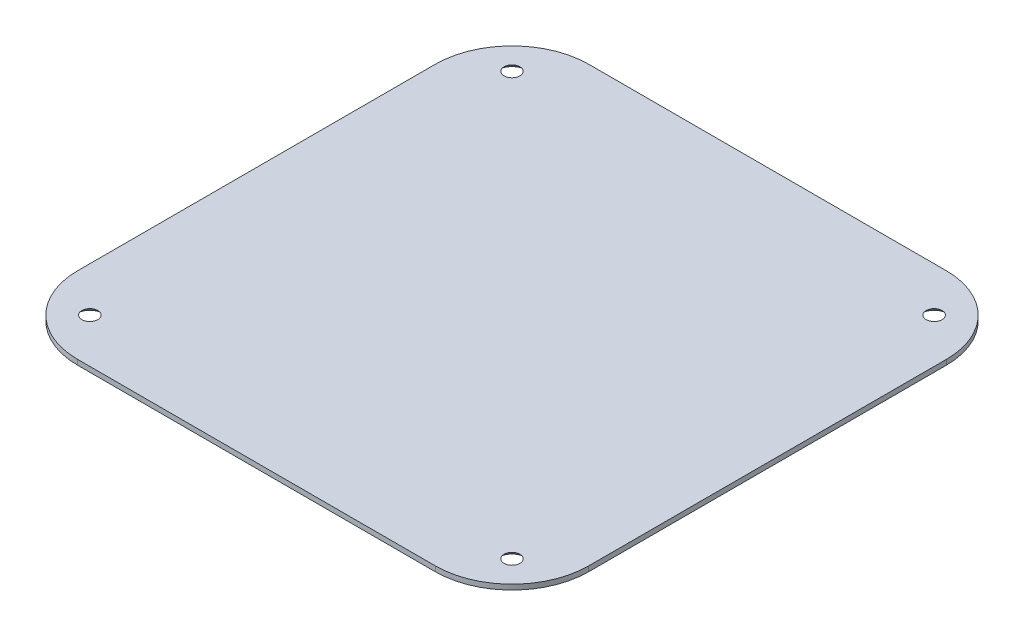
SolidWorks part; units mm, degrees
ref_plane "Front Plane" through (0, 0, 0) normal (0, 0, 1) x (1, 0, 0)
ref_plane "Top Plane" through (0, 0, 0) normal (0, 1, 0) x (1, 0, 0)
ref_plane "Right Plane" through (0, 0, 0) normal (1, 0, 0) x (0, 0, -1)
sketch "Sketch1" plane through (0, 0, 0) normal (0, 1, 0) x (1, 0, 0)
  line L0 (-80, 100) -> (-80, -100) construction
  line L15 (70, -100) -> (-70, -100)
  line L16 (100, -70) -> (100, 70)
  line L17 (70, 100) -> (-70, 100)
  line L18 (-100, -70) -> (-100, 70)
  line L35 (100, -100) -> (-100, 100) construction
  line L45 (100, 100) -> (-100, -100) construction
  line L46 (80, 100) -> (80, -100) construction
  line L53 (-100, 80) -> (100, 80) construction
  line L54 (-100, -80) -> (100, -80) construction
  line L82 (-100, 0) -> (100, 0) construction
  line L83 (-100, 40) -> (100, 40) construction
  line L120 (-100, -40) -> (100, -40) construction
  line L121 (0, 100) -> (0, -100) construction
  line L122 (-40, 100) -> (-40, -100) construction
  line L123 (40, 100) -> (40, -100) construction
  line L124 (-42.5, 70) -> (-42.5, 50)
  line L125 (-50, 2.5) -> (-70, 2.5)
  line L126 (-42.5, 10) -> (-42.5, 30)
  line L127 (-50, 37.5) -> (-70, 37.5)
  line L128 (-77.5, 10) -> (-77.5, 30)
  line L129 (-42.5, 2.5) -> (-77.5, 37.5) construction
  line L130 (-42.5, 37.5) -> (-77.5, 2.5) construction
  line L131 (-50, 42.5) -> (-70, 42.5)
  line L132 (-77.5, 70) -> (-77.5, 50)
  line L133 (-50, 77.5) -> (-70, 77.5)
  line L134 (-30, 77.5) -> (-10, 77.5)
  line L135 (-2.5, 70) -> (-2.5, 50)
  line L136 (-37.5, 70) -> (-37.5, 50)
  line L137 (-30, 42.5) -> (-10, 42.5)
  line L138 (-30, 37.5) -> (-10, 37.5)
  line L139 (-37.5, 10) -> (-37.5, 30)
  line L140 (-30, 2.5) -> (-10, 2.5)
  line L141 (-2.5, 10) -> (-2.5, 30)
  line L142 (42.5, 10) -> (42.5, 30)
  line L143 (50, 2.5) -> (70, 2.5)
  line L144 (77.5, 10) -> (77.5, 30)
  line L145 (50, 37.5) -> (70, 37.5)
  line L146 (42.5, 70) -> (42.5, 50)
  line L147 (50, 77.5) -> (70, 77.5)
  line L148 (77.5, 70) -> (77.5, 50)
  line L149 (50, 42.5) -> (70, 42.5)
  line L150 (2.5, 70) -> (2.5, 50)
  line L151 (30, 77.5) -> (10, 77.5)
  line L152 (37.5, 70) -> (37.5, 50)
  line L153 (30, 42.5) -> (10, 42.5)
  line L154 (37.5, 10) -> (37.5, 30)
  line L155 (30, 37.5) -> (10, 37.5)
  line L156 (2.5, 10) -> (2.5, 30)
  line L157 (30, 2.5) -> (10, 2.5)
  line L158 (-42.5, -70) -> (-42.5, -50)
  line L159 (-50, -77.5) -> (-70, -77.5)
  line L160 (-77.5, -70) -> (-77.5, -50)
  line L161 (-50, -42.5) -> (-70, -42.5)
  line L162 (-2.5, -70) -> (-2.5, -50)
  line L163 (-30, -77.5) -> (-10, -77.5)
  line L164 (-37.5, -70) -> (-37.5, -50)
  line L165 (-30, -42.5) -> (-10, -42.5)
  line L166 (37.5, -70) -> (37.5, -50)
  line L167 (30, -77.5) -> (10, -77.5)
  line L168 (2.5, -70) -> (2.5, -50)
  line L169 (30, -42.5) -> (10, -42.5)
  line L170 (77.5, -70) -> (77.5, -50)
  line L171 (50, -77.5) -> (70, -77.5)
  line L172 (42.5, -70) -> (42.5, -50)
  line L173 (50, -42.5) -> (70, -42.5)
  line L174 (50, -37.5) -> (70, -37.5)
  line L175 (77.5, -10) -> (77.5, -30)
  line L176 (50, -2.5) -> (70, -2.5)
  line L177 (42.5, -10) -> (42.5, -30)
  line L178 (37.5, -10) -> (37.5, -30)
  line L179 (30, -2.5) -> (10, -2.5)
  line L180 (2.5, -10) -> (2.5, -30)
  line L181 (30, -37.5) -> (10, -37.5)
  line L182 (-30, -37.5) -> (-10, -37.5)
  line L183 (-37.5, -10) -> (-37.5, -30)
  line L184 (-2.5, -10) -> (-2.5, -30)
  line L185 (-30, -2.5) -> (-10, -2.5)
  line L186 (-42.5, -10) -> (-42.5, -30)
  line L187 (-50, -37.5) -> (-70, -37.5)
  line L188 (-77.5, -10) -> (-77.5, -30)
  line L189 (-50, -2.5) -> (-70, -2.5)
  arc A0 (100, 70) -> (70, 100) centre (70, 70) ccw
  arc A1 (70, -100) -> (100, -70) centre (70, -70) ccw
  arc A2 (-70, -100) -> (-100, -70) centre (-70, -70) cw
  arc A3 (-70, 100) -> (-100, 70) centre (-70, 70) ccw
  circle A5 centre (-82.6, 82.6) radius 2.6
  circle A6 centre (82.6, 82.6) radius 2.6
  circle A7 centre (82.6, -82.6) radius 2.6
  circle A8 centre (-82.6, -82.6) radius 2.6
  arc A9 (-70, 2.5) -> (-77.5, 10) centre (-70, 10) cw
  arc A10 (-50, 2.5) -> (-42.5, 10) centre (-50, 10) ccw
  arc A11 (-42.5, 30) -> (-50, 37.5) centre (-50, 30) ccw
  arc A12 (-70, 37.5) -> (-77.5, 30) centre (-70, 30) ccw
  arc A13 (-50, 77.5) -> (-42.5, 70) centre (-50, 70) cw
  arc A14 (-42.5, 50) -> (-50, 42.5) centre (-50, 50) cw
  arc A15 (-70, 42.5) -> (-77.5, 50) centre (-70, 50) cw
  arc A16 (-70, 77.5) -> (-77.5, 70) centre (-70, 70) ccw
  arc A17 (-30, 77.5) -> (-37.5, 70) centre (-30, 70) ccw
  arc A18 (-10, 77.5) -> (-2.5, 70) centre (-10, 70) cw
  arc A19 (-37.5, 50) -> (-30, 42.5) centre (-30, 50) ccw
  arc A20 (-10, 42.5) -> (-2.5, 50) centre (-10, 50) ccw
  arc A21 (-10, 37.5) -> (-2.5, 30) centre (-10, 30) cw
  arc A22 (-37.5, 30) -> (-30, 37.5) centre (-30, 30) cw
  arc A23 (-30, 2.5) -> (-37.5, 10) centre (-30, 10) cw
  arc A24 (-10, 2.5) -> (-2.5, 10) centre (-10, 10) ccw
  arc A25 (42.5, 30) -> (50, 37.5) centre (50, 30) cw
  arc A26 (50, 2.5) -> (42.5, 10) centre (50, 10) cw
  arc A27 (70, 2.5) -> (77.5, 10) centre (70, 10) ccw
  arc A28 (70, 37.5) -> (77.5, 30) centre (70, 30) cw
  arc A29 (50, 77.5) -> (42.5, 70) centre (50, 70) ccw
  arc A30 (70, 77.5) -> (77.5, 70) centre (70, 70) cw
  arc A31 (70, 42.5) -> (77.5, 50) centre (70, 50) ccw
  arc A32 (42.5, 50) -> (50, 42.5) centre (50, 50) ccw
  arc A33 (10, 42.5) -> (2.5, 50) centre (10, 50) cw
  arc A34 (10, 77.5) -> (2.5, 70) centre (10, 70) ccw
  arc A35 (30, 77.5) -> (37.5, 70) centre (30, 70) cw
  arc A36 (37.5, 50) -> (30, 42.5) centre (30, 50) cw
  arc A37 (37.5, 30) -> (30, 37.5) centre (30, 30) ccw
  arc A38 (10, 37.5) -> (2.5, 30) centre (10, 30) ccw
  arc A39 (10, 2.5) -> (2.5, 10) centre (10, 10) cw
  arc A40 (30, 2.5) -> (37.5, 10) centre (30, 10) ccw
  arc A41 (-42.5, -50) -> (-50, -42.5) centre (-50, -50) ccw
  arc A42 (-50, -77.5) -> (-42.5, -70) centre (-50, -70) ccw
  arc A43 (-70, -77.5) -> (-77.5, -70) centre (-70, -70) cw
  arc A44 (-70, -42.5) -> (-77.5, -50) centre (-70, -50) ccw
  arc A45 (-10, -77.5) -> (-2.5, -70) centre (-10, -70) ccw
  arc A46 (-30, -77.5) -> (-37.5, -70) centre (-30, -70) cw
  arc A47 (-37.5, -50) -> (-30, -42.5) centre (-30, -50) cw
  arc A48 (-10, -42.5) -> (-2.5, -50) centre (-10, -50) cw
  arc A49 (37.5, -50) -> (30, -42.5) centre (30, -50) ccw
  arc A50 (30, -77.5) -> (37.5, -70) centre (30, -70) ccw
  arc A51 (10, -77.5) -> (2.5, -70) centre (10, -70) cw
  arc A52 (10, -42.5) -> (2.5, -50) centre (10, -50) ccw
  arc A53 (70, -42.5) -> (77.5, -50) centre (70, -50) cw
  arc A54 (70, -77.5) -> (77.5, -70) centre (70, -70) ccw
  arc A55 (50, -77.5) -> (42.5, -70) centre (50, -70) cw
  arc A56 (42.5, -50) -> (50, -42.5) centre (50, -50) cw
  arc A57 (70, -37.5) -> (77.5, -30) centre (70, -30) ccw
  arc A58 (70, -2.5) -> (77.5, -10) centre (70, -10) cw
  arc A59 (50, -2.5) -> (42.5, -10) centre (50, -10) ccw
  arc A60 (42.5, -30) -> (50, -37.5) centre (50, -30) ccw
  arc A61 (37.5, -30) -> (30, -37.5) centre (30, -30) cw
  arc A62 (30, -2.5) -> (37.5, -10) centre (30, -10) cw
  arc A63 (10, -2.5) -> (2.5, -10) centre (10, -10) ccw
  arc A64 (10, -37.5) -> (2.5, -30) centre (10, -30) cw
  arc A65 (-10, -37.5) -> (-2.5, -30) centre (-10, -30) ccw
  arc A66 (-37.5, -30) -> (-30, -37.5) centre (-30, -30) ccw
  arc A67 (-10, -2.5) -> (-2.5, -10) centre (-10, -10) cw
  arc A68 (-30, -2.5) -> (-37.5, -10) centre (-30, -10) ccw
  arc A69 (-50, -2.5) -> (-42.5, -10) centre (-50, -10) cw
  arc A70 (-42.5, -30) -> (-50, -37.5) centre (-50, -30) cw
  arc A71 (-70, -37.5) -> (-77.5, -30) centre (-70, -30) cw
  arc A72 (-70, -2.5) -> (-77.5, -10) centre (-70, -10) ccw
  point P0 (0, 0)
  point P25 (-60, 20)
  dimension "D3" = 20
  dimension "D5" = 20
  dimension "D4" = 20
  dimension "D22" = 5.2
  dimension "D15" = 30
  dimension "D16" = 5.2
  dimension "D19" = 5.2
  dimension "D20" = 5.2
  dimension "D24" = 7.5
  dimension "D1" = 200
  dimension "D2" = 200
  dimension "D6" = 20
  dimension "D7" = 40
  dimension "D8" = 40
  dimension "D9" = 40
  dimension "D10" = 40
  dimension "D11" = 20
  dimension "D12" = 20
  dimension "D13" = 35
  dimension "D14" = 35
  dimension "D17" = 2.6
  dimension "D18" = 2.6
  dimension "D21" = 2.6
  dimension "D23" = 2.6
extrude "Boss-Extrude1" add sketch "Sketch1" along normal blind 2 contours A7 | A8 | A5 | A6 | L15 A2 L18 A3 L17 A0 L16 A1 region at (-82.6, 0, -82.6) region at (82.6, 0, -82.6) region at (82.6, 0, 82.6) region at (-82.6, 0, 82.6)
extrude "Cut-Extrude1" cut sketch "Sketch1<3>" along normal blind 0.1 contours L152 L154 L155 | L144 | A36 L152 A35 L151 A34 L150 A33 L153 | L137 A20 L135 A18 L134 A17 L136 A19 | L140 A24 L141 A21 L138 A22 L139 A23 | L185 A68 L183 A66 L182 A65 L184 A67 | A64 L181 A61 L178 A62 L179 A63 L180 | L157 A40 L154 A37 L155 A38 L156 A39 | A28 L145 A25 L142 A26 L143 A27 L144 | L177 A60 L174 A57 L175 A58 L176 A59 | L146 A32 L149 A31 L148 A30 L147 A29 | A56 L172 A55 L171 A54 L170 A53 L173 | L169 A52 L168 A51 L167 A50 L166 A49 | L127 A12 L128 A9 L125 A10 L126 A11 | L133 A16 L132 A15 L131 A14 L124 A13 | L189 A72 L188 A71 L187 A70 L186 A69 | L161 A44 L160 A43 L159 A42 L158 A41 | A48 L165 A47 L164 A46 L163 A45 L162 region at (-60, 0, -60) region at (-60, 0, -20) region at (-20, 0, -60) region at (-20, 0, -20) region at (60, 0, -20) region at (60, 0, -60) region at (20, 0, -60) region at (20, 0, -20) region at (-60, 0, 60) region at (-20, 0, 60) region at (20, 0, 60) region at (60, 0, 60) region at (60, 0, 20) region at (20, 0, 20) region at (-20, 0, 20) region at (-60, 0, 20)
sketch "Sketch1<3>" plane through (0, 0, 0) normal (0, 1, 0) x (1, 0, 0) same geometry as "Sketch1"
chamfer "Chamfer1" distance 2.5 4 edges at (-82.6, 0, -80) (-82.6, 0, 85.2) (82.6, 0, 85.2) (82.6, 0, -80)
